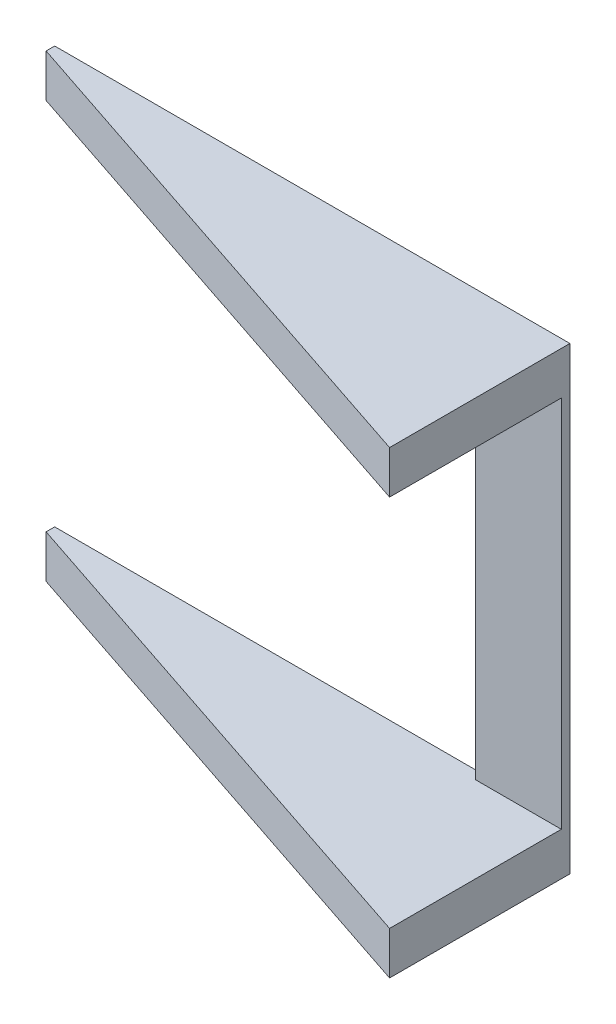
SolidWorks part; units mm, degrees
ref_plane "Front Plane" through (0, 0, 0) normal (0, 0, 1) x (1, 0, 0)
ref_plane "Top Plane" through (0, 0, 0) normal (0, 1, 0) x (1, 0, 0)
ref_plane "Right Plane" through (0, 0, 0) normal (1, 0, 0) x (0, 0, -1)
sketch "Sketch1" plane through (0, 0, 0) normal (0, 0, 1) x (1, 0, 0)
  line L0 (-33.5419, 109.9376) -> (-33.5419, 2.9376)
  line L1 (-153.5419, 99.9376) -> (-53.5419, 99.9376)
  line L3 (-153.5419, 12.9376) -> (-53.5419, 12.9376)
  line L4 (-53.5419, 99.9376) -> (-53.5419, 12.9376)
  line L5 (-153.5419, 56.4376) -> (-53.5419, 12.9376) construction
  line L6 (-153.5419, 56.4376) -> (-53.5419, 99.9376) construction
  line L7 (-33.5419, 2.9376) -> (-153.5419, 2.9376)
  line L9 (-153.5419, 109.9376) -> (-33.5419, 109.9376)
  line L10 (-153.5419, 109.9376) -> (-153.5419, 99.9376)
  line L11 (-153.5419, 12.9376) -> (-153.5419, 2.9376)
  point P0 (-153.5419, 56.4376)
  point P11 (0, 0)
  dimension "D1" = 100
  dimension "D2" = 87
  dimension "D3" = 10
  dimension "D4" = 10
  dimension "D5" = 20
extrude "Boss-Extrude1" add sketch "Sketch1" along normal blind 2
sketch "Sketch2" plane through (0, 109.9376, 0) normal (0, 1, 0) x (1, 0, 0)
  line L0 (-153.5419, -2) -> (-33.5419, -2)
  line L1 (-33.5419, -2) -> (-33.5419, -42)
  line L2 (-33.5419, -42) -> (-153.5419, -2)
  line L3 (-53.5419, -2) -> (-53.5419, -35.3333) construction
  dimension "D1" = 40
extrude "Boss-Extrude2" add sketch "Sketch2" against normal blind 10
extrude "Boss-Extrude3" add sketch "Sketch2<2>" along normal blind 10 from surface starting at face at (-93.5419, 2.9376, 1)
sketch "Sketch2<2>" plane through (0, 109.9376, 0) normal (0, 1, 0) x (1, 0, 0) same geometry as "Sketch2"
